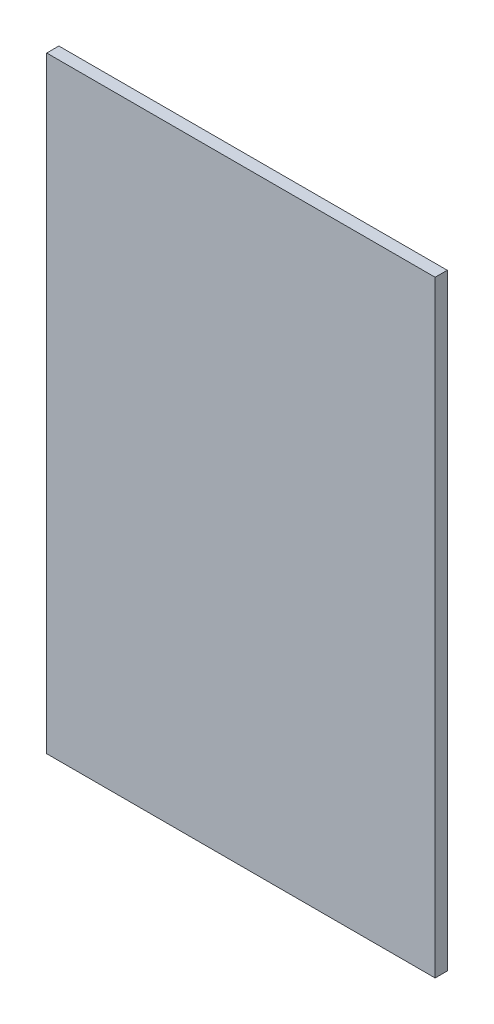
SolidWorks part; units mm, degrees
ref_plane "Front Plane" through (0, 0, 0) normal (0, 0, 1) x (1, 0, 0)
ref_plane "Top Plane" through (0, 0, 0) normal (0, 1, 0) x (1, 0, 0)
ref_plane "Right Plane" through (0, 0, 0) normal (1, 0, 0) x (0, 0, -1)
sketch "Sketch1" plane through (0, 0, 0) normal (0, 0, 1) x (1, 0, 0)
  line L1 (0, 0) -> (-203.2, 0)
  line L2 (0, 0) -> (0, 317.5)
  line L3 (0, 317.5) -> (-203.2, 317.5)
  line L4 (-203.2, 0) -> (-203.2, 317.5)
  dimension "D1" = 317.5
  dimension "D2" = 203.2
extrude "Boss-Extrude1" add sketch "Sketch1" along normal blind 6.35
